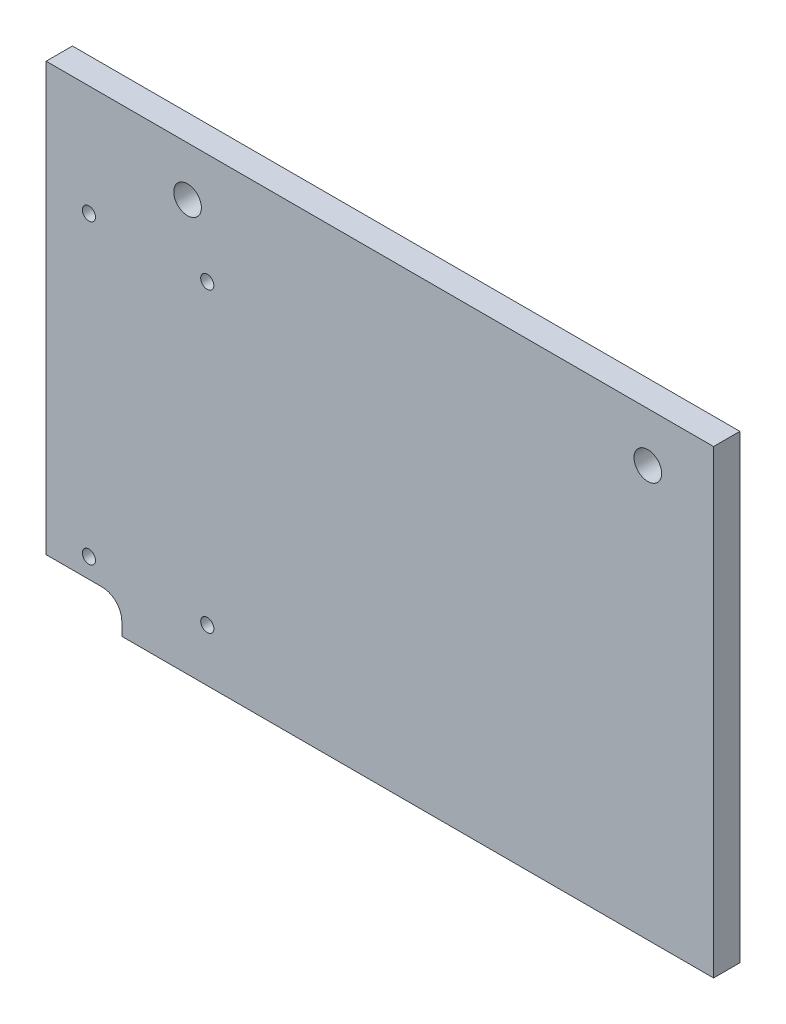
SolidWorks part; units mm, degrees
material "默认 (3)"
ref_plane "前视基准面" through (0, 0, 0) normal (0, 0, 1) x (1, 0, 0)
ref_plane "上视基准面" through (0, 0, 0) normal (0, 1, 0) x (1, 0, 0)
ref_plane "右视基准面" through (0, 0, 0) normal (1, 0, 0) x (0, 0, -1)
other "Configuration Table"
sketch "草图1" plane through (0, 0, 0) normal (0, 0, 1) x (1, 0, 0)
  line L0 (0, 0) -> (0, -50000) construction
  line L1 (-125, 15) -> (125, 15)
  line L2 (-125, 15) -> (-125, -15)
  line L3 (-125, -15) -> (125, -15)
  line L4 (125, 15) -> (125, -15)
  line L5 (-125, 15) -> (125, -15) construction
  line L6 (-125, -15) -> (125, 15) construction
  line L7 (-115, -10) -> (-115, 10) construction
  circle A0 centre (-115, -10) radius 1.5
  circle A1 centre (-115, 10) radius 1.5
  circle A2 centre (115, 10) radius 1.5
  circle A3 centre (115, -10) radius 1.5
  point P0 (0, 0)
  dimension "D6" = 5
  dimension "D7" = 3
  dimension "D1" = 250
  dimension "D2" = 30
  dimension "D4" = 20
  dimension "D5" = 10
  dimension "D3" = 2
extrude "凸台-拉伸1" add sketch "草图1" along normal blind 4
sketch "草图2" plane through (0, 0, 4) normal (0, 0, 1) x (1, 0, 0)
  line L0 (0, 0) -> (0, -50000) construction
  line L1 (0, 9) -> (50000, 9) construction
  line L2 (-23, 2.5) -> (23, 2.5) construction
  line L3 (-23, 2.5) -> (-23, 15.5) construction
  line L4 (-125, -15) -> (125, -15) construction
  circle A0 centre (-23, 2.5) radius 3
  circle A1 centre (23, 2.5) radius 3
  circle A2 centre (23, 15.5) radius 3
  circle A3 centre (-23, 15.5) radius 3
  dimension "D5" = 6
  dimension "D3" = 46
  dimension "D4" = 13
  dimension "D6" = 24
  dimension "D1" = 2
  dimension "D2" = 2
extrude "切除-拉伸1" cut sketch "草图2" against normal through all
sketch "草图3" plane through (0, 0, 4) normal (0, 0, 1) x (1, 0, 0)
  line L0 (0, 54.5) -> (0, -49945.5) construction
  line L1 (-125, 85) -> (125, 85)
  line L2 (-125, 85) -> (-125, 15)
  line L3 (-125, 15) -> (125, 15)
  line L4 (125, 85) -> (125, 15)
  line L5 (-125, 85) -> (125, 15) construction
  line L6 (-125, 15) -> (125, 85) construction
  line L8 (-115, 10) -> (-115, 30) construction
  circle A4 centre (-115, 10) radius 1.5 construction
  circle A5 centre (-115, 10) radius 1.5
  circle A6 centre (-115, 30) radius 1.5
  circle A7 centre (-115, 50) radius 1.5
  circle A8 centre (-115, 70) radius 1.5
  circle A9 centre (-115, 90) radius 1.5
  circle A10 centre (115, 10) radius 1.5
  circle A11 centre (115, 30) radius 1.5
  circle A12 centre (115, 50) radius 1.5
  circle A13 centre (115, 70) radius 1.5
  circle A14 centre (-35, 77.5) radius 2.1
  circle A15 centre (35, 77.5) radius 2.1
  point P0 (0, 50)
  line M16 (125, 15) -> (25.958, 15)
  dimension "D4" = 70
  dimension "D2" = 4.2
  dimension "D3" = 7.5
  dimension "D1" = 70
  dimension "D7" = 20
  dimension "D6" = 5
extrude "凸台-拉伸2" add sketch "草图3" against normal blind 4 contours L4 L1 L2 A12 A14 A6 A7 A8 A11 A13 M16 region at (0, 49.9563, 4)
sketch "草图4" plane through (0, 0, 4) normal (0, 0, 1) x (1, 0, 0)
  line L1 (-125, 85) -> (125, 85) construction
  line L8 (-125, -15) -> (125, -15) construction
  line L9 (-97, 70) -> (-48, 70)
  line L10 (-100, 67) -> (-100, 3)
  line L11 (-97, 0) -> (-48, 0)
  line L12 (-45, 67) -> (-45, 3)
  line L13 (-100, 70) -> (-45, 0) construction
  line L14 (-100, 0) -> (-45, 70) construction
  line L15 (-125, 85) -> (-125, -15) construction
  line L16 (97, 0) -> (48, 0)
  line L17 (45, 67) -> (45, 3)
  line L18 (97, 70) -> (48, 70)
  line L19 (100, 67) -> (100, 3)
  arc A4 (-48, 0) -> (-45, 3) centre (-48, 3) ccw
  arc A5 (-100, 3) -> (-97, 0) centre (-97, 3) ccw
  arc A6 (-48, 70) -> (-45, 67) centre (-48, 67) cw
  arc A7 (-97, 70) -> (-100, 67) centre (-97, 67) ccw
  arc A8 (48, 0) -> (45, 3) centre (48, 3) cw
  arc A9 (48, 70) -> (45, 67) centre (48, 67) ccw
  arc A10 (100, 3) -> (97, 0) centre (97, 3) cw
  arc A11 (97, 70) -> (100, 67) centre (97, 67) cw
  point P10 (-72.5, 35)
  dimension "D4" = 15
  dimension "D5" = 15
  dimension "D6" = 25
  dimension "D7" = 55
extrude "切除-拉伸2" cut sketch "草图4" against normal through all
fillet "圆角1" radius 5 4 edges at (125, -15, 2) (125, 85, 2) (-125, -15, 2) (-125, 85, 2)
sketch "草图5" plane through (0, 0, 4) normal (0, 0, 1) x (1, 0, 0)
  circle A0 centre (-23, 15.5) radius 3
  circle A1 centre (23, 15.5) radius 3
  dimension "D1" = 6
extrude "切除-拉伸3" cut sketch "草图5" against normal through all
sketch "草图8" plane through (0, 0, 4) normal (0, 0, 1) x (1, 0, 0)
  line L0 (-48, 70) -> (-97, 70) construction
  line L1 (-45, 70) -> (-65, 70)
  line L2 (-45, 70) -> (-45, 20)
  line L3 (-45, 20) -> (-65, 20)
  line L4 (-65, 70) -> (-65, 20)
  line L5 (-45, 3) -> (-45, 67) construction
  dimension "D1" = 50
  dimension "D2" = 20
extrude "凸台-拉伸4" add sketch "草图8" against normal up to surface (4 mm away) up to face at (-72.5, 35, 0)
sketch "草图9" plane through (0, 0, 4) normal (0, 0, 1) x (1, 0, 0)
  line L0 (-65, 20) -> (-45, 20) construction
  line L1 (-65, 70) -> (-65, 20) construction
  circle A0 centre (-50, 23) radius 1
  circle A1 centre (-32, 23) radius 1
  circle A2 centre (-50, 68.2) radius 1
  circle A3 centre (-32, 68.2) radius 1
  dimension "D1" = 2
  dimension "D4" = 3
  dimension "D5" = 15
  dimension "D2" = 2
  dimension "D3" = 2
extrude "切除-拉伸4" cut sketch "草图9" against normal blind 10
fillet "圆角3" radius 3 3 edges at (-45, 20, 2) (-65, 70, 2) (-65, 20, 2)
sketch "草图10" plane through (0, 0, 4) normal (0, 0, 1) x (1, 0, 0)
  line L0 (0, 0) -> (0, 130.9934) construction
  line L1 (35, 15) -> (35, -15)
  line L2 (35, 15) -> (-35, 15)
  line L3 (0, 15) -> (0, -15)
  line L4 (35, -15) -> (-35, -15)
  line L5 (-35, 15) -> (-35, -15)
  line L6 (-120, -15) -> (120, -15) construction
  dimension "D1" = 70
  dimension "D2" = 30
  dimension "D3" = 30
extrude "切除-拉伸5" cut sketch "草图10" against normal blind 10 contours L2 L5 L4 L3 | L4 L1 L2 L3 region at (17.5, 0, 4) region at (-17.5, 0, 4)
sketch "草图11" plane through (0, 0, 4) normal (0, 0, 1) x (1, 0, 0)
  line L1 (-35, 15) -> (35, 15)
  line L2 (-35, 15) -> (-35, 19.6041)
  line L3 (-35, 19.6041) -> (35, 19.6041)
  line L4 (35, 15) -> (35, 19.6041)
extrude "凸台-拉伸5" add sketch "草图11" against normal up to surface (4 mm away) up to face at (-31, 23, 0)
fillet "圆角4" radius 10 4 edges at (35, 15, 2) (35, -15, 2) (-35, -15, 2) (-35, 15, 2)
sketch "草图12" plane through (0, 0, 4) normal (0, 0, 1) x (1, 0, 0)
  line L0 (0, 85) -> (0, -53.6278) construction
  line L1 (-120, 85) -> (120, 85) construction
  line L2 (-159.4821, 67) -> (-159.4821, 15)
  line L3 (45, 67) -> (144.5907, 67)
  line L4 (45, 67) -> (45, 102.3315)
  line L5 (45, 102.3315) -> (144.5907, 102.3315)
  line L6 (144.5907, 67) -> (144.5907, 102.3315)
  line L7 (45, 67) -> (137.7054, 67)
  line L8 (45, 67) -> (45, 15)
  line L11 (25, 15) -> (159.4821, 15)
  line L12 (25, 15) -> (25, -21.4432)
  line L13 (25, -21.4432) -> (159.4821, -21.4432)
  line L14 (159.4821, 15) -> (159.4821, -21.4432)
  line L15 (45, 67) -> (159.4821, 67)
  line L16 (45, 67) -> (45, 15)
  line L17 (45, 15) -> (159.4821, 15)
  line L18 (159.4821, 67) -> (159.4821, 15)
  line L19 (-45, 15) -> (-159.4821, 15)
  line L20 (-56.5072, 67) -> (-56.5072, 15)
  line L21 (-56.5072, 67) -> (-159.4821, 67)
  line L22 (-159.4821, 15) -> (-159.4821, -21.4432)
  line L23 (-25, -21.4432) -> (-159.4821, -21.4432)
  line L24 (-25, 15) -> (-25, -21.4432)
  line L25 (-25, 15) -> (-159.4821, 15)
  line L26 (-56.5072, 67) -> (-56.5072, 102.3315)
  line L27 (-56.5072, 67) -> (-137.7054, 67)
  line L28 (-144.5907, 67) -> (-144.5907, 102.3315)
  line L29 (-56.5072, 102.3315) -> (-144.5907, 102.3315)
  line L31 (-56.5072, 67) -> (-144.5907, 67)
extrude "切除-拉伸6" cut sketch "草图12" against normal blind 10 contours L21 L29 L28 | L21 L2 L19 | L24 L25 L19 L22 L23 | L3 L6 L5 L4 | L18 L15 L3 L8 L11 | L14 L11 L12 L13 region at (-107.9946, 41, 4) region at (-92.241, -3.2216, 4) region at (-100.5489, 84.6658, 4) region at (94.7953, 84.6658, 4) region at (102.241, 41, 4) region at (92.241, -3.2216, 4)
